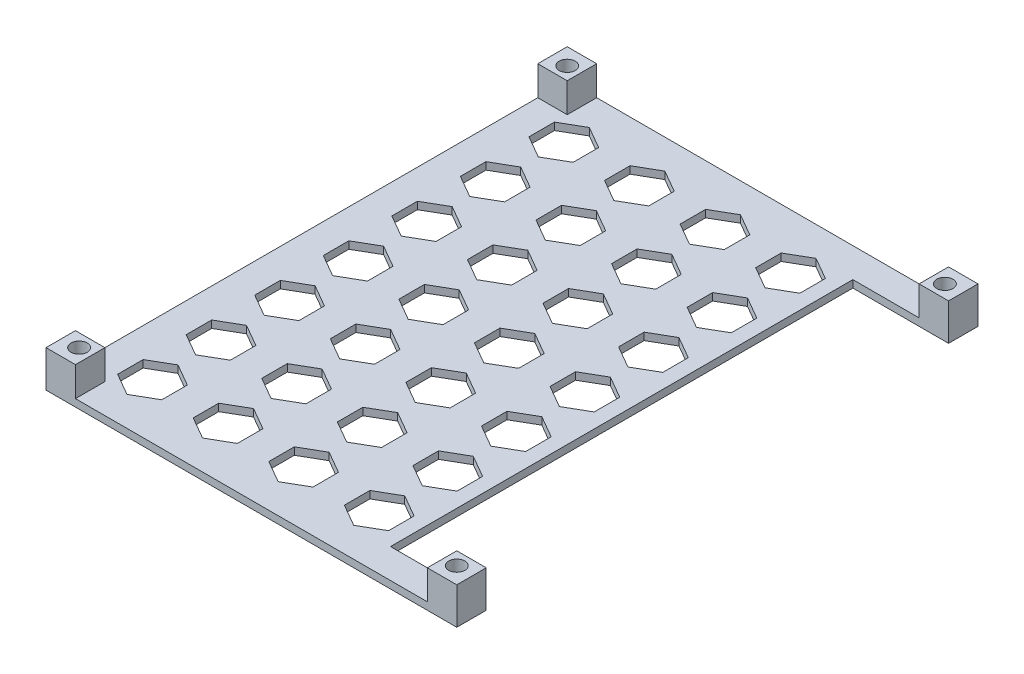
SolidWorks part; units mm, degrees
ref_plane "Front Plane" through (0, 0, 0) normal (0, 0, 1) x (1, 0, 0)
ref_plane "Top Plane" through (0, 0, 0) normal (0, 1, 0) x (1, 0, 0)
ref_plane "Right Plane" through (0, 0, 0) normal (1, 0, 0) x (0, 0, -1)
sketch "Sketch1" plane through (0, 0, 0) normal (0, 1, 0) x (1, 0, 0)
  line L0 (0, 0) -> (55.8, 0)
  line L5 (55.8, 0) -> (55.8, 4)
  line L6 (55.8, 4) -> (42.8, 4)
  line L7 (42.8, 4) -> (42.8, 66.8)
  line L8 (42.8, 66.8) -> (55.8, 66.8)
  line L9 (55.8, 66.8) -> (55.8, 70.8)
  line L10 (55.8, 70.8) -> (0, 70.8)
  line L11 (0, 70.8) -> (0, 0)
  dimension "D1" = 55.8
  dimension "D2" = 13
  dimension "D3" = 70.8
  dimension "D4" = 4
  dimension "D5" = 4
extrude "Boss-Extrude1" add sketch "Sketch1" along normal blind 1
sketch "Sketch2" plane through (0, 1, 0) normal (0, 1, 0) x (1, 0, 0)
  line L0 (42.8, 66.8) -> (0, 66.8) construction
  line L1 (0, 70.8) -> (0, 0) construction
  line L2 (4, 70.8) -> (4, 0) construction
  line L3 (55.8, 70.8) -> (0, 70.8) construction
  line L5 (0, 0) -> (55.8, 0) construction
  line L6 (40.8, 66.8) -> (40.8, 0) construction
  line L7 (42.8, 4) -> (42.8, 66.8) construction
  line L9 (7, 66.8) -> (4, 65.0679)
  line L10 (4, 65.0679) -> (4, 61.6038)
  line L11 (4, 61.6038) -> (7, 59.8718)
  line L12 (7, 59.8718) -> (10, 61.6038)
  line L13 (10, 61.6038) -> (10, 65.0679)
  line L14 (10, 65.0679) -> (7, 66.8)
  circle A0 centre (7, 63.3359) radius 3 construction
  dimension "D1" = 4
  dimension "D2" = 2
  dimension "D3" = 6
extrude "Cut-Extrude1" cut sketch "Sketch2" against normal up to surface (1 mm away) up to face at (38.6, 0, -35.4)
pattern_linear "LPattern1" count 4 spacing 10.2667 along (1, 0, 0) count 7 spacing 9.312 along (0, 0, 1) of "Cut-Extrude1"
sketch "Sketch3" plane through (0, 1, 0) normal (0, 1, 0) x (1, 0, 0)
  line L0 (42.8, 66.8) -> (55.8, 66.8) construction
  line L1 (0, 70.8) -> (4, 70.8)
  line L2 (0, 70.8) -> (0, 66.8)
  line L3 (0, 66.8) -> (4, 66.8)
  line L4 (4, 70.8) -> (4, 66.8)
  line L5 (55.8, 70.8) -> (51.8, 70.8)
  line L6 (55.8, 70.8) -> (55.8, 66.8)
  line L7 (55.8, 66.8) -> (51.8, 66.8)
  line L8 (51.8, 70.8) -> (51.8, 66.8)
  line L9 (0, 0) -> (55.8, 0) construction
  line L10 (55.8, 4) -> (51.8, 4)
  line L11 (55.8, 4) -> (55.8, 0)
  line L12 (55.8, 0) -> (51.8, 0)
  line L13 (51.8, 4) -> (51.8, 0)
  line L15 (0, 0) -> (4, 0)
  line L16 (0, 0) -> (0, 4)
  line L17 (0, 4) -> (4, 4)
  line L18 (4, 0) -> (4, 4)
  dimension "D1" = 4
extrude "Boss-Extrude2" add sketch "Sketch3" along normal blind 4
sketch "Sketch4" plane through (0, 5, 0) normal (0, 1, 0) x (1, 0, 0)
  line L3 (0, 68.55) -> (55.8, 68.55) construction
  line L4 (0, 70.8) -> (0, 66.8) construction
  line L5 (55.8, 66.8) -> (55.8, 70.8) construction
  line L6 (4, 70.8) -> (0, 70.8) construction
  circle A0 centre (2.25, 68.55) radius 1.1
  circle A1 centre (53.55, 68.55) radius 1.1
  dimension "D3" = 2.2
  dimension "D1" = 2.25
  dimension "D2" = 2.25
  dimension "D4" = 2.25
extrude "Cut-Extrude2" cut sketch "Sketch4" against normal up to surface (5 mm away) up to face at (17.2667, 0, -63.3359)
ref_plane "Plane1" through (0, 0, -35.4) normal (0, 0, -1) x (-1, 0, 0)
mirror "Mirror1" about plane through (0, 0, -35.4) normal (0, 0, -1) of "Cut-Extrude2"
